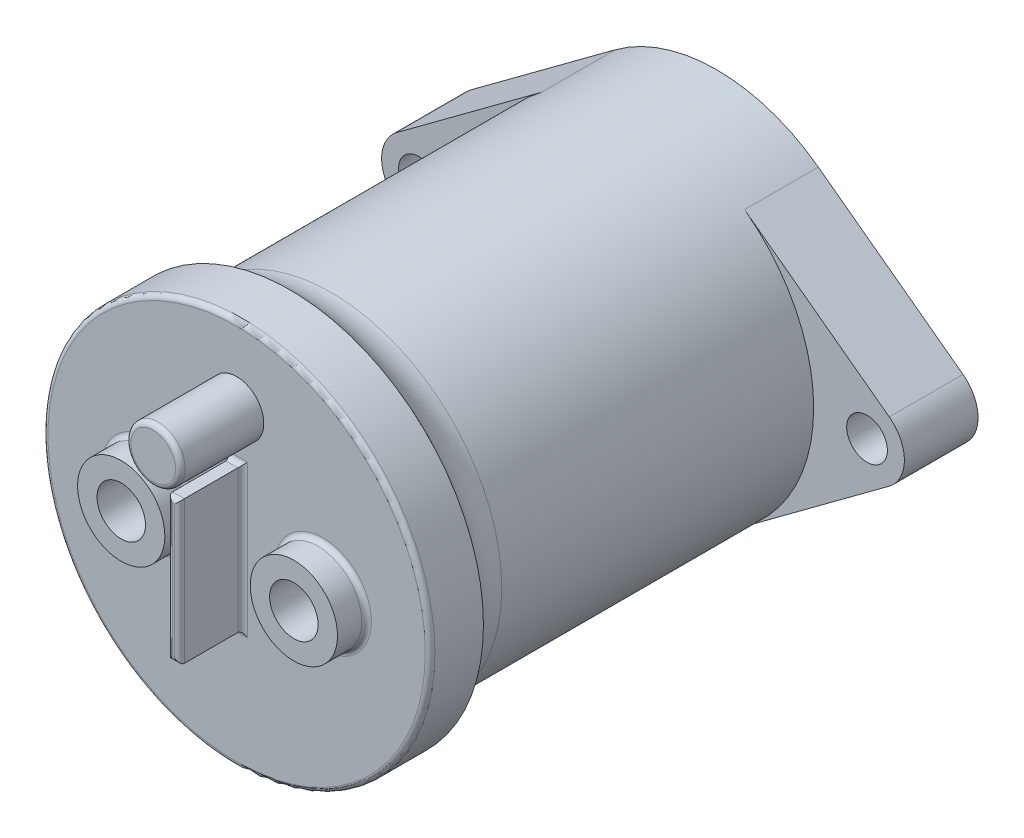
SolidWorks part; units mm, degrees
material "Custom Plastic"
ref_plane "X-Y Datum" through (0, 0, 0) normal (0, 0, 1) x (1, 0, 0)
ref_plane "X-Z Datum" through (0, 0, 0) normal (0, 1, 0) x (1, 0, 0)
ref_plane "Y-Z Datum" through (0, 0, 0) normal (1, 0, 0) x (0, 0, -1)
sketch "Sketch2" plane through (0, 0, 0) normal (0, 0, 1) x (1, 0, 0)
  circle A0 centre (0, 0) radius 17.6
  dimension "D1" = 35.2
extrude "Boss-Extrude1" add sketch "Sketch2" along normal blind 52.5
sketch "Sketch3" plane through (0, 0, 0) normal (0, 0, 1) x (1, 0, 0)
  line L0 (-23.1, 0) -> (23.1, 0) construction
  line L1 (-26.95, 0) -> (26.95, 0) construction
  line L2 (-25.3917, 3.0937) -> (-10.4762, 14.1425)
  line L3 (-25.3917, -3.0937) -> (-10.4762, -14.1425)
  line L4 (0, 28.5555) -> (0, -28.5555) construction
  line L5 (25.3917, -3.0937) -> (10.4762, -14.1425)
  line L6 (25.3917, 3.0937) -> (10.4762, 14.1425)
  circle A0 centre (23.1, 0) radius 2.1
  circle A1 centre (-23.1, 0) radius 2.1
  circle A2 centre (23.1, 0) radius 3.85
  circle A3 centre (-23.1, 0) radius 3.85
  circle A6 centre (0, 0) radius 17.6 construction
  circle A8 centre (0, 0) radius 17.6
  circle A9 centre (0, 0) radius 17.6
  point P4 (0, 0)
  point P10 (0, 0)
  point P23 (0, 0)
  dimension "D2" = 4.2
  dimension "D1" = 46.2
  dimension "D3" = 53.9
  dimension "D4" = 0
extrude "Boss-Extrude2" add sketch "Sketch3" along normal blind 7.6 contours A9 A2 L6 | A9 L5 A2 | A9 A2 A0 | A9 A3 A1 | A9 A3 L3 | A9 L2 A3 region at (-18.5342, 0, 0) region at (-21.417, 3.3412, 0) region at (18.5342, 0, 0) region at (26.4412, 1.683, 0)
sketch "Sketch4" plane through (0, 0, 52.5) normal (0, 0, 1) x (1, 0, 0)
  line L0 (-8.9, 0) -> (8.9, 0) construction
  line L1 (-0.615, 7.35) -> (0.615, 7.35)
  line L2 (-0.615, 7.35) -> (-0.615, -7.35)
  line L3 (-0.615, -7.35) -> (0.615, -7.35)
  line L4 (0.615, 7.35) -> (0.615, -7.35)
  line L5 (-0.615, 7.35) -> (0.615, -7.35) construction
  line L6 (-0.615, -7.35) -> (0.615, 7.35) construction
  circle A0 centre (-8.9, 0) radius 2.5
  circle A1 centre (8.9, 0) radius 2.5
  circle A2 centre (-8.9, 0) radius 4.5
  circle A3 centre (8.9, 0) radius 4.5
  point P0 (0, 0)
  point P11 (0, 0)
  dimension "D4" = 5
  dimension "D5" = 9
  dimension "D1" = 1.23
  dimension "D2" = 14.7
  dimension "D3" = 17.8
extrude "Boss-Extrude3" add sketch "Sketch4" along normal blind 3.5 contours L2 L1 L4 L3
sketch "Sketch5" plane through (0, 0, 52.5) normal (0, 0, 1) x (1, 0, 0)
  line L4 (0.615, 7.35) -> (-0.615, 7.35)
  line L5 (0.615, -7.35) -> (0.615, 7.35)
  line L6 (-0.615, -7.35) -> (0.615, -7.35)
  line L7 (-0.615, 7.35) -> (-0.615, -7.35)
  line L8 (0.615, 7.35) -> (-0.615, 7.35)
  line L9 (0.615, -7.35) -> (0.615, 7.35)
  line L10 (-0.615, -7.35) -> (0.615, -7.35)
  line L11 (-0.615, 7.35) -> (-0.615, -7.35)
  circle A1 centre (8.9, 0) radius 4.5
  circle A2 centre (8.9, 0) radius 4.5
  circle A3 centre (-8.9, 0) radius 4.5
  circle A4 centre (-8.9, 0) radius 4.5
  circle A5 centre (8.9, 0) radius 2.5
  circle A6 centre (8.9, 0) radius 2.5
  circle A7 centre (-8.9, 0) radius 2.5
  circle A8 centre (-8.9, 0) radius 2.5
  circle M22 centre (0, 0) radius 17.6
  line M23 (0.615, 7.35) -> (0.615, -7.35)
  line M24 (0.615, -7.35) -> (-0.615, -7.35)
  line M25 (-0.615, -7.35) -> (-0.615, 7.35)
  line M26 (-0.615, 7.35) -> (0.615, 7.35)
  dimension "D1" = 0
  dimension "D2" = 0
  dimension "D3" = 0
  dimension "D4" = 0
  dimension "D5" = 0
extrude "Cut-Extrude1" cut sketch "Sketch5" against normal blind 3 contours A4 A2 M22 M26 M23 M24 M25 | A8 | A6 region at (8.9, 0, 52.5) region at (-8.9, 0, 52.5) region at (-17.1022, 0, 52.5)
sketch "Sketch7" plane through (0, 0, 49.5) normal (0, 0, 1) x (1, 0, 0)
  circle A0 centre (0, 0) radius 19.95
  dimension "D1" = 39.9
extrude "Boss-Extrude5" add sketch "Sketch7" against normal blind 5.5
fillet "Fillet3" radius 5 1 edges at (17.6, 0, 44)
fillet "Fillet4" radius 0.5 11 edges at (-0.615, 0, 56) (0, 7.35, 56) (0.615, 0, 56) (0, -7.35, 56) (19.95, 0, 49.5) (-0.615, 0, 49.5) (0, -7.35, 49.5) (0.615, 0, 49.5) (0, 7.35, 49.5) (13.4, 0, 49.5) (-4.4, 0, 49.5)
sketch "Sketch8" plane through (0, 0, 52.5) normal (0, 0, 1) x (1, 0, 0)
  circle A0 centre (-8.9, 0) radius 2.5 construction
  circle A1 centre (8.9, 0) radius 2.5
  circle A2 centre (8.9, 0) radius 2.5
  circle A3 centre (-8.9, 0) radius 2.5
  dimension "D1" = 0
extrude "Cut-Extrude2" cut sketch "Sketch8" against normal blind 7
ref_plane "Plane1" through (0, 0, 0) normal (0.8035, 0.5952, 0) x (0, 0, 1)
sketch "Sketch10" plane through (0, 0, 49.5) normal (0, 0, 1) x (1, 0, 0)
  line L0 (0, 0) -> (0, 12.15) construction
  line L1 (0.615, 7.35) -> (-0.615, 7.35) construction
  circle A0 centre (0, 12.15) radius 2.8
  point P2 (0, 9.35)
  dimension "D1" = 5.6
  dimension "D2" = 2
extrude "Boss-Extrude6" add sketch "Sketch10" along normal blind 8.6
fillet "Fillet5" radius 0.5 1 edges at (2.8, 12.15, 58.1)
ref_plane "Plane3" through (0, 0, 0) normal (0.8035, 0.5952, 0) x (0, 0, -1)
